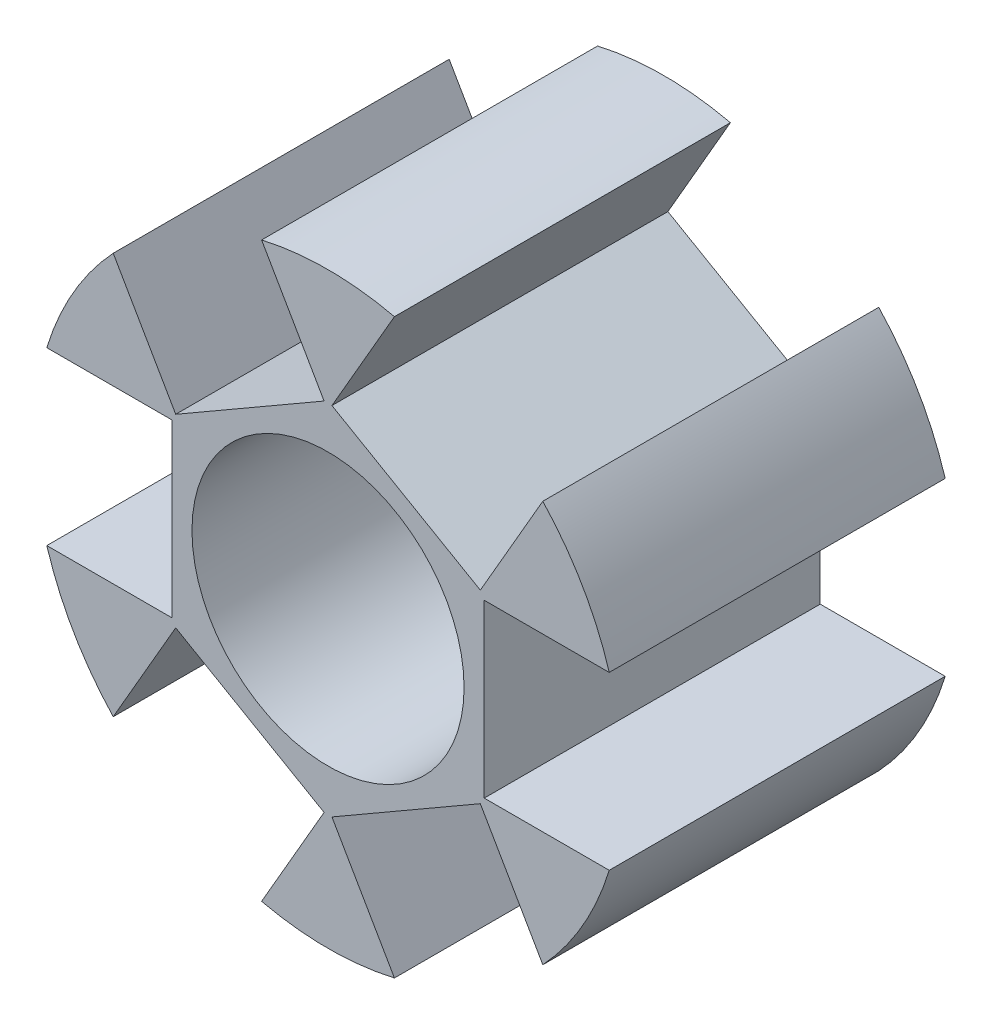
SolidWorks part; units mm, degrees
ref_plane "Top Plane" through (0, 0, 0) normal (0, 0, 1) x (1, 0, 0)
ref_plane "Right Plane" through (0, 0, 0) normal (0, 1, 0) x (1, 0, 0)
ref_plane "Front Plane" through (0, 0, 0) normal (1, 0, 0) x (0, 0, -1)
ref_axis "x-axis" through (-88.99, 0, 0) along (1, 0, 0)
ref_axis "y-axis" through (0, -55, 0) along (0, 1, 0)
ref_axis "z-axis" through (0, 0, 55) along (0, 0, -1)
sketch "Sketch1" plane through (0, 0, 0) normal (0, 0, 1) x (1, 0, 0)
  line L8 (-19.9785, 0) -> (0, 0) construction
  line L16 (0, 0) -> (0, -20.7846) construction
  line L23 (0, 0) -> (0, -20.7846) construction
  circle A0 centre (0, 0) radius 4.05
  circle A3 centre (0, 0) radius 8.75
  dimension "D1" = 8.1
  dimension "D2" = 17.5
extrude "Boss-Extrude1" add sketch "Sketch1" along normal mid plane 10
ref_plane "Plane1" through (-8.75, 0, 0) normal (-1, 0, 0) x (0, 0, 1)
sketch "Sketch2" plane through (-8.75, -17.1931, 0) normal (1, 0, 0) x (0, -1, 0)
  line L1 (-19.7431, -5) -> (-14.6431, -5)
  line L2 (-19.7431, -5) -> (-19.7431, 5)
  line L3 (-19.7431, 5) -> (-14.6431, 5)
  line L4 (-14.6431, -5) -> (-14.6431, 5)
  line L5 (-19.7431, -5) -> (-14.6431, 5) construction
  line L6 (-19.7431, 5) -> (-14.6431, -5) construction
  point P0 (-17.1931, 0)
  dimension "D1" = 5.1
  dimension "D2" = 10
extrude "Cut-Extrude3" cut sketch "Sketch2" along normal blind 4.1
pattern_circular "CirPattern1" count 6 over 360 about axis through (0, 0, 5) along (0, 0, 1) of "Cut-Extrude3"
